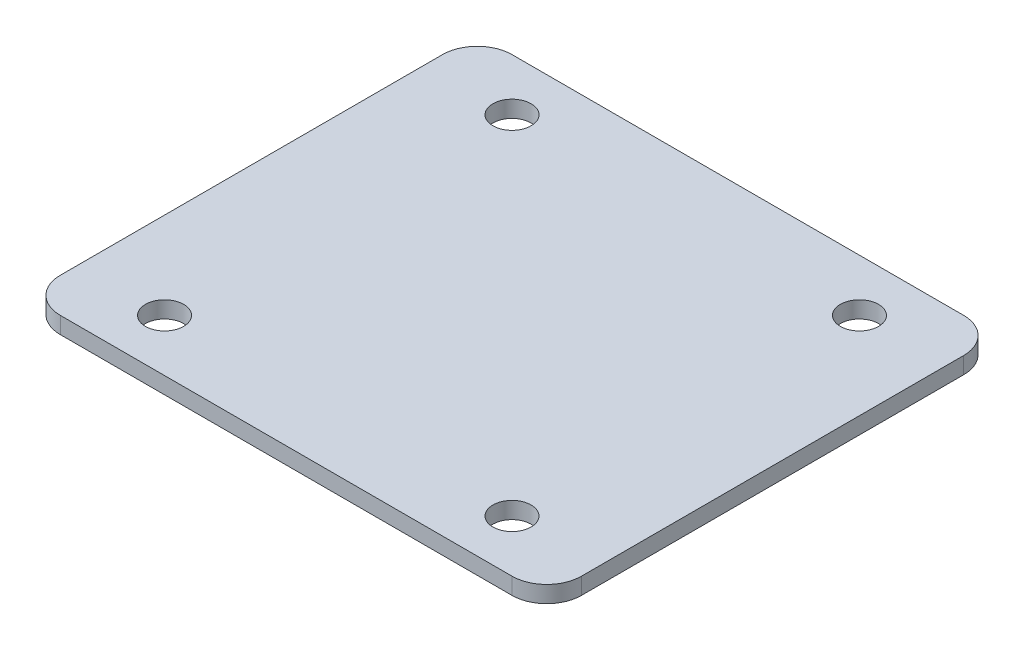
SolidWorks part; units mm, degrees
material "AISI 1020"
ref_plane "Plano frontal" through (0, 0, 0) normal (0, 0, 1) x (1, 0, 0)
ref_plane "Plano superior" through (0, 0, 0) normal (0, 1, 0) x (1, 0, 0)
ref_plane "Plano direito" through (0, 0, 0) normal (1, 0, 0) x (0, 0, -1)
sketch "Esboço1" plane through (0, 0, 0) normal (0, 1, 0) x (1, 0, 0)
  line L5 (-50, -50) -> (50, -50) construction
  line L6 (-50, -50) -> (-50, 50) construction
  line L15 (-50, 50) -> (50, 50) construction
  line L16 (50, -50) -> (50, 50) construction
  line L17 (-50, -50) -> (50, 50) construction
  line L18 (-50, 50) -> (50, -50) construction
  line L19 (-65, -65) -> (65, -65)
  line L20 (-75, -55) -> (-75, 55)
  line L21 (-65, 65) -> (65, 65)
  line L22 (75, -55) -> (75, 55)
  line L23 (-75, -65) -> (75, 65) construction
  line L24 (-75, 65) -> (75, -65) construction
  arc A4 (65, 65) -> (75, 55) centre (65, 55) cw
  arc A5 (75, -55) -> (65, -65) centre (65, -55) cw
  arc A6 (-65, -65) -> (-75, -55) centre (-65, -55) cw
  arc A7 (-75, 55) -> (-65, 65) centre (-65, 55) cw
  circle A8 centre (-50, 50) radius 5.5
  circle A9 centre (50, 50) radius 5.5
  circle A10 centre (50, -50) radius 5.5
  circle A11 centre (-50, -50) radius 5.5
  point P0 (0, 0)
  point P6 (0, 0)
  dimension "D3" = 150
  dimension "D5" = 10
  dimension "D6" = 11
  dimension "D1" = 100
  dimension "D2" = 100
  dimension "D4" = 130
base flange "Flange-base1" sketch "Esboço1" thickness 4.8 reverse thickness direction no parameters "D1"=5
sketch "Curva-Linhas1" [suppressed] plane through (0, 0, 0) normal (0, 1, 0) x (1, 0, 0)
sketch "Caixa delimitadora1" [suppressed] plane through (0, 0, 0) normal (0, 1, 0) x (1, 0, 0)
sheet metal parameters "Chapa metálica1" thickness 4.8 parameters "D1"=5
flat pattern "Padrão-Plano1" [suppressed]
sketch "Curva-Linhas2" plane through (0, 0, 0) normal (0, 1, 0) x (1, 0, 0)
sketch3d "Caixa delimitadora2" [suppressed]
  line L0 (140, 10, 0) -> (-10, 10, 0) construction
  line L1 (140, -120, 0) -> (-10, -120, 0) construction
  line L2 (140, 10, 0) -> (140, -120, 0) construction
  line L3 (-10, 10, 0) -> (-10, -120, 0) construction
